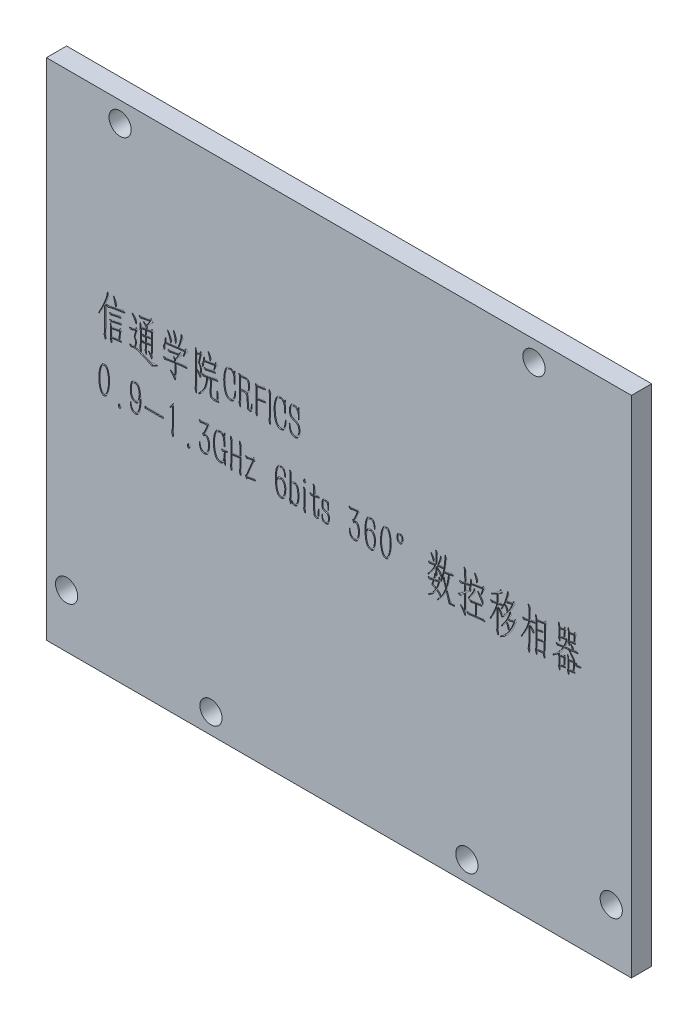
SolidWorks part; units mm, degrees
material "6061-T6 (SS)"
ref_plane "前视基准面" through (0, 0, 0) normal (0, 0, 1) x (1, 0, 0)
ref_plane "上视基准面" through (0, 0, 0) normal (0, 1, 0) x (1, 0, 0)
ref_plane "右视基准面" through (0, 0, 0) normal (1, 0, 0) x (0, 0, -1)
other "Configuration Table"
sketch "草图1" plane through (0, 0, 0) normal (0, 0, 1) x (1, 0, 0)
  line L1 (-4.3, -4.3) -> (53.65, -4.3)
  line L2 (-4.3, -4.3) -> (-4.3, 45.68)
  line L3 (-4.3, 45.68) -> (53.65, 45.68)
  line L4 (53.65, -4.3) -> (53.65, 45.68)
  dimension "D1" = 53.65
  dimension "D2" = 4.3
  dimension "D3" = 45.68
  dimension "D4" = 4.3
extrude "Main_Stock" add sketch "草图1" along normal blind 2 from offset 11.1
sketch "草图2" plane through (0, 0, 13.1) normal (0, 0, 1) x (1, 0, 0)
  circle A0 centre (-2.3, 1) radius 1.1
  circle A1 centre (51.65, 1) radius 1.1
  circle A2 centre (12, -2.3) radius 1.1
  circle A3 centre (37.35, -2.3) radius 1.1
  circle A4 centre (3, 43.68) radius 1.1
  circle A5 centre (44, 43.68) radius 1.1
  dimension "D1" = 2.2
  dimension "D2" = 3
  dimension "D3" = 12
  dimension "D4" = 37.35
  dimension "D5" = 44
  dimension "D6" = 51.65
  dimension "D7" = 2.3
  dimension "D8" = 1
  dimension "D9" = 43.68
  dimension "D10" = 2.3
extrude "Cover_6xD2p2_Through" cut sketch "草图2" against normal through all
sketch "草图3" plane through (0, 0, 13.1) normal (0, 0, 1) x (1, 0, 0)
  text T0 "信通学院CRFICS\r\n0.9-1.3GHz 6bits 360°数控移相器" font "汉仪长仿宋体" height 3
extrude "切除-拉伸1" cut sketch "草图3" against normal blind 0.1
